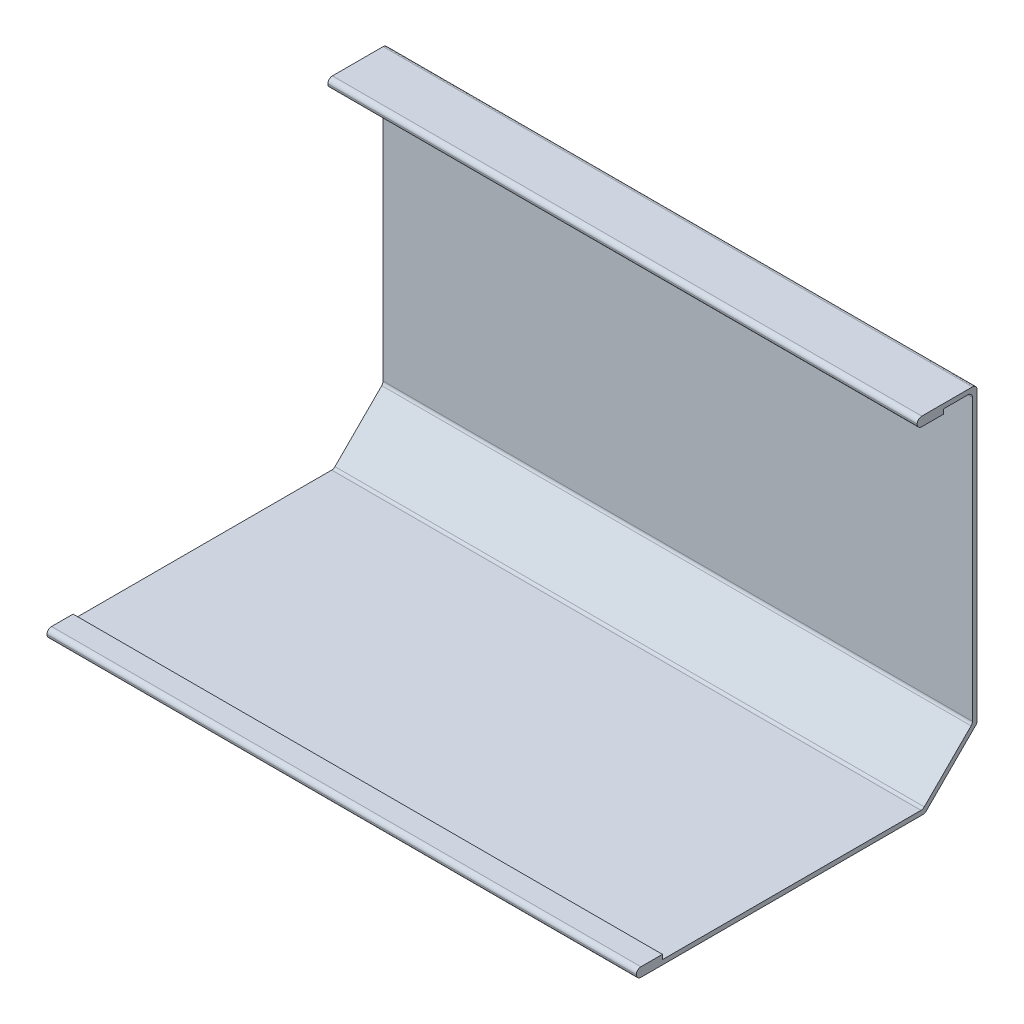
SolidWorks part; units mm, degrees
ref_plane "前基準面" through (0, 0, 0) normal (0, 0, 1) x (1, 0, 0)
ref_plane "上基準面" through (0, 0, 0) normal (0, 1, 0) x (1, 0, 0)
ref_plane "右基準面" through (0, 0, 0) normal (1, 0, 0) x (0, 0, -1)
ref_plane "平面1"
sketch "草圖1" plane through (0, 0, 0) normal (1, 0, 0) x (0, 1, 0)
  line L0 (0, 17) -> (1.5, 17)
  line L1 (1.5, 17) -> (1.5, 17.6213)
  line L2 (1.5, 17.6213) -> (0, 17)
  line L3 (17, 0) -> (17.6213, 1.5)
  line L4 (17.6213, 1.5) -> (17, 1.5)
  line L5 (17, 1.5) -> (17, 0)
  line L6 (1.5, 111) -> (1.5, 102.5)
  line L7 (1.5, 102.5) -> (3, 102.5)
  line L8 (3, 102.5) -> (3, 111)
  line L9 (3, 111) -> (1.5, 111)
  line L10 (111.1, 19.5) -> (109.6, 19.5)
  line L11 (109.6, 19.5) -> (109.6, 11)
  line L12 (109.6, 11) -> (111.1, 11)
  line L13 (111.1, 11) -> (111.1, 19.5)
  line L14 (112.6, 1.5) -> (112.6, 19.5)
  line L15 (112.6, 19.5) -> (111.1, 19.5)
  line L16 (111.1, 19.5) -> (111.1, 1.5)
  line L17 (111.1, 1.5) -> (112.6, 1.5)
  line L18 (0, 17) -> (17, 0)
  line L19 (17, 0) -> (17, 1.5)
  line L20 (17, 1.5) -> (17.6213, 1.5)
  line L21 (17.6213, 1.5) -> (1.5, 17.6213)
  line L22 (1.5, 17.6213) -> (1.5, 17)
  line L23 (1.5, 17) -> (0, 17)
  line L24 (0, 17) -> (1.5, 17.6213)
  line L25 (1.5, 17.6213) -> (1.5, 111)
  line L26 (1.5, 111) -> (0, 111)
  line L27 (0, 111) -> (0, 17)
  line L28 (17, 0) -> (112.6, 0)
  line L29 (112.6, 0) -> (112.6, 1.5)
  line L30 (112.6, 1.5) -> (17.6213, 1.5)
  line L31 (17.6213, 1.5) -> (17, 0)
extrude "擠出1" add sketch "草圖1" along normal blind 96 and the other way blind 96 contours L1 L2 L0 | L4 L5 L3 | L8 L9 L6 L7 | L12 L13 L10 L11 | L16 L17 L14 L15 L13 | L4 L21 L1 L0 L18 L5 | L26 L27 L2 L25 L6 | L17 L30 L3 L28 L29 region at (0, 1, 17.2071) region at (0, 0.7492, 64.1552) region at (0, 9.0235, 9.0235) region at (0, 17.2071, 1) region at (0, 64.9552, 0.7492) region at (0, 2.25, 106.75) region at (0, 111.85, 10.5) region at (0, 110.35, 15.25)
fillet "圓角1" radius 1.5 10 edges at (0, 0, 111) (0, 3, 111) (0, 1.5, 17.6213) (0, 17, 0) (0, 0, 17) (0, 17.6213, 1.5) (0, 111.1, 1.5) (0, 112.6, 0) (0, 109.6, 19.5) (0, 112.6, 19.5)
